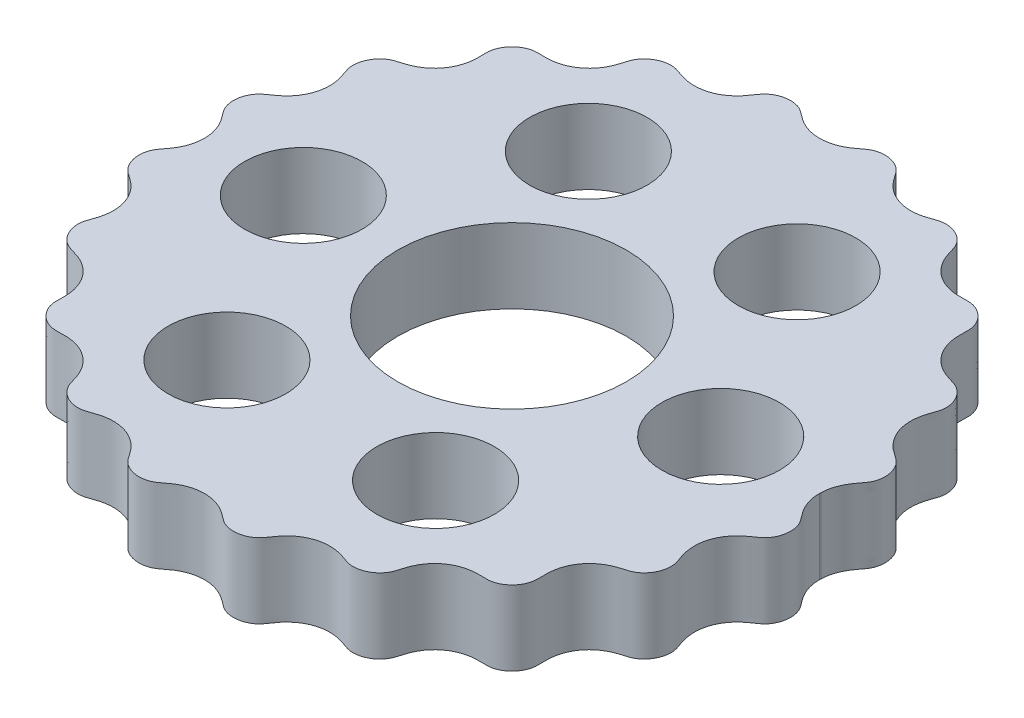
SolidWorks part; units mm, degrees
ref_plane "Front Plane" through (0, 0, 0) normal (0, 0, 1) x (1, 0, 0)
ref_plane "Top Plane" through (0, 0, 0) normal (0, 1, 0) x (1, 0, 0)
ref_plane "Right Plane" through (0, 0, 0) normal (1, 0, 0) x (0, 0, -1)
sketch "Cycloidal Base Sketch" plane through (0, 0, 0) normal (0, 1, 0) x (1, 0, 0)
  circle A0 centre (0, 0) radius 10.4
  spline S0 degree 4 poles (26.8059, 13.4572) (26.8639, 13.3205) (26.9582, 13.0381) (27.0247, 12.6393) (26.9913, 12.1833) (26.8931, 11.8403) (26.7874, 11.5481) (26.6811, 11.2558) (26.5654, 10.8802) (26.4695, 10.4144) (26.427, 9.9103) (26.4544, 9.3746) (26.5579, 8.8368) (26.741, 8.3075) (27.0736, 7.6723) (27.5036, 7.1396) (27.9833, 6.7262) (28.4638, 6.3979) (28.7892, 6.1843) (29.1138, 5.8878) (29.3918, 5.4852) (29.5767, 5.0325) (29.6654, 4.5525) (29.6681, 4.114) (29.6085, 3.728) (29.4888, 3.368) (29.3103, 3.046) (29.0925, 2.7659) (28.8808, 2.4963) (28.6821, 2.2162) (28.5035, 1.9231) (28.3483, 1.6165) (28.2193, 1.2987) (28.1286, 1.0033) (28.0684, 0.7391) (28.031, 0.4991) (28.0098, 0.3153) (27.9999, 0.0887) (27.9991, -0.0272) (28.0029, -0.1486) (28.0089, -0.265) (28.0175, -0.3782) (28.0354, -0.5324) (28.0698, -0.744) (28.1249, -0.9884) (28.2083, -1.2608) (28.3108, -1.5275) (28.4323, -1.7855) (28.5865, -2.0656) (28.7812, -2.3612) (29.0137, -2.6715) (29.2824, -2.9979) (29.5111, -3.3993) (29.6506, -3.8796) (29.6859, -4.4152) (29.5951, -4.9837) (29.3933, -5.4827) (29.1084, -5.8975) (28.762, -6.2072) (28.4035, -6.4354) (28.0263, -6.7018) (27.6432, -7.0237) (27.1801, -7.5243) (26.7185, -8.267) (26.4119, -9.2525) (26.4126, -10.2383) (26.5911, -11.0032) (26.7882, -11.5548) (26.927, -11.9205) (27.0435, -12.4984) (26.9493, -13.2923) (26.5792, -14.0112) (25.9799, -14.554) (25.4261, -14.7937) (25.0319, -14.8958) (24.5986, -15.0296) (24.1341, -15.2147) (23.6554, -15.4803) (23.1843, -15.841) (22.6738, -16.3739) (22.2038, -17.1251) (21.9508, -17.9268) (21.889, -18.705) (21.9078, -19.2869) (21.9249, -19.6752) (21.8711, -20.1112) (21.7056, -20.5711) (21.3378, -21.1537) (20.842, -21.5737) (20.3424, -21.8097) (19.8501, -21.9053) (19.5428, -21.9221) (19.1848, -21.902) (18.7291, -21.8953) (18.227, -21.9313) (17.5411, -22.0688) (16.7174, -22.4135) (15.8912, -23.0484) (15.3236, -23.8571) (15.0299, -24.5755) (14.8707, -25.1317) (14.766, -25.5035) (14.5781, -25.8973) (14.2781, -26.2796) (13.8632, -26.6219) (13.3335, -26.8852) (12.7989, -27.0092) (12.2906, -27.0113) (11.8436, -26.9022) (11.4606, -26.7512) (11.0257, -26.6054) (10.534, -26.4858) (9.8342, -26.4087) (8.9432, -26.4893) (8.1017, -26.7955) (7.3751, -27.2965) (6.9023, -27.7769) (6.6066, -28.1555) (6.3661, -28.5133) (6.1518, -28.8317) (5.8503, -29.1436) (5.4485, -29.4103) (4.9529, -29.6037) (4.3781, -29.688) (3.8872, -29.6483) (3.4999, -29.5378) (3.2176, -29.4051) (3.0274, -29.2892) (2.8036, -29.124) (2.5433, -28.9157) (2.201, -28.6662) (1.7577, -28.406) (1.2527, -28.191) (0.6884, -28.0437) (-0.0326, -27.9684) (-0.7557, -28.0384) (-1.4479, -28.2507) (-2.0404, -28.5633) (-2.4351, -28.8321) (-2.7715, -29.0973) (-3.073, -29.3309) (-3.4554, -29.5298) (-3.9177, -29.6561) (-4.4471, -29.6846) (-5.0196, -29.5854) (-5.5263, -29.3716) (-5.9011, -29.0996) (-6.1494, -28.8243) (-6.3429, -28.5502) (-6.5277, -28.2703) (-6.7787, -27.9261) (-7.1239, -27.5413) (-7.5425, -27.1814) (-8.039, -26.8689) (-8.7082, -26.5782) (-9.4242, -26.4275) (-10.1535, -26.4235) (-10.8129, -26.5457) (-11.2651, -26.6821) (-11.6572, -26.8284) (-12.0036, -26.9493) (-12.4193, -27.0163) (-12.8932, -26.9935) (-13.4055, -26.8567) (-13.9224, -26.5824) (-14.2973, -26.2558) (-14.5452, -25.9324) (-14.6935, -25.6538) (-14.7772, -25.4447) (-14.8598, -25.1759) (-14.9496, -24.8509) (-15.0843, -24.4441) (-15.2974, -23.9699) (-15.5891, -23.4974) (-15.9703, -23.0471) (-16.413, -22.6624) (-16.906, -22.3515) (-17.4366, -22.1197) (-17.9918, -21.9687) (-18.5102, -21.9036) (-18.9796, -21.8955) (-19.3952, -21.9141) (-19.7601, -21.9199) (-20.1734, -21.8522) (-20.6133, -21.6828) (-21.056, -21.3934) (-21.4613, -20.9716) (-21.716, -20.5431) (-21.8505, -20.1561) (-21.9036, -19.8431) (-21.9171, -19.6171) (-21.9114, -19.3343) (-21.8968, -18.9956) (-21.9008, -18.5646) (-21.96, -18.0451) (-22.0957, -17.5034) (-22.3246, -16.9559) (-22.6319, -16.4545) (-23.0085, -16.01) (-23.4431, -15.6306) (-23.9235, -15.3209) (-24.3946, -15.103) (-24.8364, -14.9529) (-25.2353, -14.8436) (-25.5816, -14.7347) (-25.9501, -14.5407) (-26.3123, -14.2435) (-26.6414, -13.8314) (-26.8948, -13.3044) (-27.0029, -12.8166) (-27.0091, -12.4045) (-26.9605, -12.0891) (-26.9016, -11.8691) (-26.8075, -11.6008) (-26.6887, -11.2811) (-26.5601, -10.8672) (-26.458, -10.3514) (-26.4232, -9.7908) (-26.4764, -9.1964) (-26.6191, -8.6243) (-26.8445, -8.0873) (-27.1437, -7.5965) (-27.5055, -7.1591) (-27.8858, -6.8108) (-28.2582, -6.5346) (-28.6022, -6.3092) (-28.8951, -6.0977) (-29.1816, -5.7989) (-29.4306, -5.4054) (-29.6132, -4.914) (-29.6894, -4.3381) (-29.6413, -3.8421) (-29.519, -3.4476) (-29.3472, -3.1076) (-29.1769, -2.8701) (-28.9943, -2.6435) (-28.7849, -2.3635) (-28.5715, -2.0475) (-28.3452, -1.633) (-28.1436, -1.1074) (-28.017, -0.526) (-27.9819, 0.0602) (-28.0354, 0.6372) (-28.1721, 1.192) (-28.3833, 1.7148) (-28.6382, 2.1591) (-28.9068, 2.5335) (-29.1632, 2.852) (-29.3734, 3.1437) (-29.5496, 3.5157) (-29.6618, 3.9648) (-29.6814, 4.4871) (-29.5742, 5.058) (-29.3729, 5.515) (-29.1317, 5.8532) (-28.9013, 6.0815) (-28.7173, 6.227) (-28.5238, 6.3592) (-28.3295, 6.4899) (-28.0903, 6.6589) (-27.7891, 6.8963) (-27.4455, 7.2241) (-27.0924, 7.6666) (-26.7946, 8.1855) (-26.5842, 8.7353) (-26.4618, 9.3014) (-26.4252, 9.8696) (-26.4682, 10.4278) (-26.5754, 10.9253) (-26.7159, 11.361) (-26.8609, 11.741) (-26.9676, 12.0823) (-27.0169, 12.4888) (-26.9825, 12.9476) (-26.8522, 13.4002) (-26.6322, 13.8255) (-26.3658, 14.1732) (-26.0763, 14.4443) (-25.7467, 14.6606) (-25.3843, 14.804) (-25.0132, 14.9019) (-24.6498, 15.0143) (-24.2055, 15.1839) (-23.698, 15.4481) (-23.1928, 15.8218) (-22.7276, 16.321) (-22.3767, 16.8567) (-22.1301, 17.403) (-21.9781, 17.9494) (-21.914, 18.4208) (-21.8983, 18.8047) (-21.9019, 19.0981) (-21.9104, 19.3326) (-21.9174, 19.5673) (-21.9082, 19.8021) (-21.8596, 20.1234) (-21.7283, 20.5183) (-21.4773, 20.9505) (-21.0789, 21.3732) (-20.6456, 21.6645) (-20.2176, 21.8382) (-19.814, 21.9152) (-19.4551, 21.9175) (-19.0475, 21.8972) (-18.5877, 21.8993) (-18.0794, 21.9532) (-17.5333, 22.0879) (-17.0042, 22.3017) (-16.5051, 22.596) (-16.0501, 22.968) (-15.6523, 23.412) (-15.3437, 23.8842) (-15.1405, 24.3114) (-15.0092, 24.6702) (-14.9231, 24.9491) (-14.8593, 25.1735) (-14.7931, 25.3975) (-14.7109, 25.6163) (-14.5642, 25.9042) (-14.3169, 26.2361) (-13.9442, 26.5673) (-13.4337, 26.8447) (-12.9296, 26.9863) (-12.4659, 27.0169) (-12.0563, 26.962) (-11.7134, 26.8503) (-11.3296, 26.7046) (-10.8884, 26.5654) (-10.3845, 26.4617) (-9.8193, 26.4248) (-9.2469, 26.4696) (-8.6797, 26.6011) (-8.1319, 26.8206) (-7.6179, 27.1262) (-7.1833, 27.4836) (-6.8246, 27.8695) (-6.5644, 28.2171) (-6.3751, 28.5015) (-6.2133, 28.736) (-6.0701, 28.9136) (-5.8435, 29.1393) (-5.5063, 29.3776) (-5.048, 29.5776) (-4.4728, 29.6829) (-3.9465, 29.6597) (-3.4939, 29.5424) (-3.1206, 29.3597) (-2.829, 29.1445) (-2.5068, 28.8863) (-2.1269, 28.6173) (-1.6752, 28.3639) (-1.144, 28.1564) (-0.5827, 28.0264) (-0.0019, 27.9813) (0.585, 28.0256) (1.164, 28.1611) (1.6834, 28.3689) (2.1399, 28.6261) (2.4919, 28.8762) (2.758, 29.0874) (2.9836, 29.2588) (3.1745, 29.3814) (3.4591, 29.5233) (3.8519, 29.643) (4.3485, 29.6895) (4.928, 29.6101) (5.4221, 29.4229) (5.8174, 29.1679) (6.1153, 28.8747) (6.3254, 28.5771) (6.5539, 28.2304) (6.8352, 27.8558) (7.1911, 27.4748) (7.6377, 27.1141) (8.1357, 26.8201) (8.6763, 26.6024) (9.2478, 26.4685) (9.8372, 26.4232) (10.3921, 26.4637) (10.9022, 26.5694) (11.3114, 26.6993) (11.6278, 26.8177) (11.8942, 26.9095) (12.1129, 26.9653) (12.4259, 27.0099) (12.834, 27.0001) (13.3192, 26.8894) (13.8452, 26.633) (14.257, 26.2998) (14.554, 25.9312) (14.7449, 25.5566) (14.8512, 25.2062) (14.9628, 24.8038) (15.1173, 24.3584) (15.4041, 23.754) (15.8339, 23.1659) (16.3749, 22.674) (17.0026, 22.3015) (17.5477, 22.0817) (18.0857, 21.9531) (18.6008, 21.899) (19.0277, 21.8976) (19.3633, 21.9128) (19.6435, 21.9166) (19.8673, 21.9006) (20.1767, 21.8445) (20.5589, 21.7078) (20.9822, 21.4527) (21.3992, 21.0485) (21.6877, 20.6041) (21.8577, 20.1572) (21.9226, 19.7321) (21.9116, 19.3517) (21.8945, 18.9246) (21.9082, 18.4482) (22.0019, 17.7864) (22.2349, 17.1018) (22.6013, 16.4748) (23.0847, 15.9341) (23.5355, 15.5623) (24.0065, 15.2784) (24.4781, 15.0715) (24.8818, 14.9405) (25.204, 14.8521) (25.4698, 14.7684) (25.6759, 14.683) (25.9502, 14.533) (26.2682, 14.2846) (26.5897, 13.9109) (26.8599, 13.3967) (26.9953, 12.8828) (27.0165, 12.402) (26.9428, 11.9755) (26.812, 11.6155) (26.6639, 11.2117) (26.531, 10.751) (26.419, 10.0878) (26.4384, 9.206) (26.6828, 8.3445) (27.1397, 7.5745) (27.6133, 7.0515) (27.9992, 6.7228) (28.3732, 6.4556) (28.7212, 6.2343) (29.0737, 5.9372) (29.3722, 5.5245) (29.587, 5.0189) (29.6859, 4.4357) (29.6537, 3.8993) (29.5217, 3.4328) (29.3154, 3.0494) (29.0766, 2.7466) (28.855, 2.4624) (28.6625, 2.1852) (28.5017, 1.9165) (28.3697, 1.659) (28.2562, 1.3927) (28.1621, 1.1193) (28.0976, 0.8742) (28.0555, 0.6601) (28.0321, 0.5046) (28.0196, 0.391) (28.0097, 0.2731) (28.0019, 0.1501) (27.999, 0.0339) (28.0017, -0.1944) (28.0172, -0.3789) (28.0404, -0.5678) (28.0694, -0.7323) (28.1083, -0.9116) (28.1593, -1.1041) (28.2315, -1.325) (28.3306, -1.5714) (28.4456, -1.8108) (28.6076, -2.1005) (28.7998, -2.3889) (29.0195, -2.6747) (29.2526, -2.9684) (29.4251, -3.2427) (29.5712, -3.5902) (29.6646, -4.0094) (29.6814, -4.6356) (29.5182, -5.2632) (29.2112, -5.7976) (28.789, -6.1854) (28.4595, -6.4) (28.104, -6.6445) (27.7365, -6.9392) (27.2807, -7.3993) (26.8581, -8.016) (26.5516, -8.7634) (26.4156, -9.6155) (26.4446, -10.2999) (26.5611, -10.8731) (26.6969, -11.301) (26.8049, -11.5957) (26.9184, -11.9123) (27.0024, -12.2627) (27.015, -12.6849) (26.9522, -13.0399) (26.88, -13.2686) (26.8371, -13.3802) knots 0 0 0 0 0 0.002533 0.005066 0.006835 0.00772 0.008605 0.010374 0.012143 0.014424 0.016705 0.018986 0.021267 0.023746 0.026226 0.031185 0.032844 0.034503 0.036162 0.037822 0.040301 0.04278 0.04444 0.046099 0.047759 0.049418 0.050882 0.052346 0.05381 0.055273 0.056737 0.058201 0.059665 0.061129 0.06199 0.062852 0.063714 0.064575 0.065184 0.065488 0.065792 0.0664 0.067009 0.068226 0.069443 0.07066 0.071876 0.073093 0.07431 0.076111 0.077913 0.079714 0.081515 0.083942 0.086368 0.088809 0.09125 0.093062 0.094873 0.096685 0.098497 0.100945 0.103394 0.108291 0.113293 0.118294 0.119961 0.121629 0.123296 0.124963 0.129954 0.134964 0.136702 0.138439 0.140177 0.141915 0.144438 0.146961 0.149485 0.152008 0.156981 0.161954 0.163611 0.165267 0.166924 0.16858 0.17106 0.17354 0.178581 0.179454 0.180328 0.182075 0.183822 0.18557 0.188108 0.190647 0.195724 0.200669 0.205614 0.20726 0.208906 0.210552 0.212197 0.214662 0.217127 0.219662 0.222197 0.223954 0.225711 0.227468 0.229224 0.231778 0.234332 0.23944 0.244357 0.246816 0.249274 0.250909 0.252544 0.254179 0.255814 0.258264 0.260713 0.263181 0.265648 0.266597 0.267546 0.268495 0.269443 0.271341 0.273239 0.275718 0.278197 0.280677 0.283156 0.288045 0.290489 0.292933 0.294557 0.296182 0.297806 0.299431 0.301865 0.304299 0.306781 0.309263 0.311171 0.312126 0.31308 0.314988 0.316897 0.319391 0.321884 0.324378 0.326872 0.331797 0.33426 0.336723 0.338285 0.339847 0.34141 0.342972 0.345429 0.347885 0.350381 0.352878 0.353837 0.354797 0.355756 0.356716 0.358635 0.360555 0.363063 0.365571 0.368079 0.370587 0.373034 0.37548 0.377927 0.380373 0.381927 0.383481 0.385035 0.386588 0.38903 0.391471 0.393982 0.396492 0.397457 0.398422 0.399387 0.400352 0.402282 0.404212 0.406735 0.409257 0.411779 0.414302 0.416732 0.419162 0.421593 0.424023 0.425568 0.427114 0.42866 0.430205 0.432631 0.435057 0.437582 0.440106 0.441077 0.442047 0.443017 0.443988 0.445929 0.44787 0.450406 0.452943 0.455479 0.458016 0.46043 0.462844 0.465258 0.467672 0.469209 0.470747 0.472284 0.473822 0.476232 0.478643 0.481152 0.483661 0.484655 0.485649 0.487638 0.488632 0.489626 0.491615 0.494144 0.496673 0.499201 0.50173 0.504128 0.506525 0.508923 0.51132 0.51285 0.514379 0.515909 0.517438 0.519834 0.522229 0.524752 0.527275 0.528275 0.529275 0.530274 0.531274 0.532274 0.533273 0.535273 0.537816 0.540358 0.542901 0.545444 0.547825 0.550206 0.552587 0.554968 0.556489 0.558011 0.559533 0.561055 0.563435 0.565816 0.567502 0.569188 0.570875 0.572561 0.574183 0.575806 0.577428 0.579051 0.582295 0.58554 0.588087 0.590635 0.593182 0.595729 0.597733 0.598734 0.599736 0.600737 0.601739 0.60274 0.603742 0.60627 0.608797 0.611188 0.613578 0.615105 0.616632 0.618159 0.619686 0.622078 0.624469 0.626861 0.629253 0.631787 0.63432 0.636854 0.639387 0.64138 0.642376 0.643372 0.644368 0.645364 0.64636 0.647356 0.64987 0.652383 0.654789 0.657195 0.658729 0.660264 0.661799 0.663334 0.665742 0.66815 0.670559 0.672967 0.675509 0.67805 0.680591 0.683133 0.685077 0.687022 0.687994 0.688966 0.689939 0.690911 0.69344 0.695969 0.69839 0.700811 0.702354 0.703897 0.70544 0.706982 0.709407 0.711832 0.714257 0.716681 0.719208 0.721736 0.724263 0.72679 0.728724 0.730658 0.731624 0.732591 0.733558 0.734525 0.73704 0.739555 0.741992 0.744428 0.745979 0.74753 0.749081 0.750632 0.753073 0.755514 0.757955 0.760396 0.762909 0.765422 0.767935 0.770448 0.772371 0.774294 0.775255 0.776216 0.777178 0.778139 0.78064 0.783141 0.785593 0.788044 0.789604 0.791163 0.792722 0.794282 0.796739 0.799196 0.804111 0.806609 0.809108 0.811607 0.814105 0.816018 0.81793 0.818886 0.819842 0.820798 0.821754 0.824241 0.826727 0.829157 0.831586 0.833207 0.834828 0.836448 0.838069 0.840509 0.842948 0.847826 0.850311 0.852795 0.855279 0.857763 0.859665 0.861566 0.862517 0.863468 0.864418 0.865369 0.867841 0.870314 0.872758 0.875202 0.876833 0.878465 0.880096 0.881728 0.884181 0.886635 0.891542 0.896661 0.89922 0.901779 0.903539 0.905299 0.907059 0.908819 0.91136 0.9139 0.91636 0.918819 0.920461 0.922103 0.923745 0.925387 0.926621 0.927855 0.929089 0.930323 0.931557 0.932791 0.933407 0.934024 0.934333 0.934641 0.935258 0.936122 0.936987 0.937851 0.938715 0.939281 0.939847 0.94098 0.942112 0.943245 0.944377 0.94551 0.947775 0.949153 0.950531 0.951909 0.953287 0.955556 0.957826 0.96251 0.964186 0.965863 0.96754 0.969216 0.971553 0.97389 0.978563 0.981882 0.9852 0.988519 0.990178 0.991837 0.992858 0.993878 0.995919 0.997959 1 1 1 1 1 construction
  spline S1 degree 4 poles (28, 0) (28, -0.031) (28.0007, -0.0776) (28.0029, -0.1486) (28.0089, -0.265) (28.0175, -0.3782) (28.0354, -0.5324) (28.0698, -0.744) (28.1249, -0.9884) (28.2083, -1.2608) (28.3108, -1.5275) (28.4323, -1.7855) (28.5865, -2.0656) (28.7812, -2.3612) (29.0137, -2.6715) (29.2824, -2.9979) (29.5111, -3.3993) (29.6506, -3.8796) (29.6859, -4.4152) (29.5951, -4.9837) (29.3933, -5.4827) (29.1084, -5.8975) (28.762, -6.2072) (28.4035, -6.4354) (28.0263, -6.7018) (27.6432, -7.0237) (27.1801, -7.5243) (26.7185, -8.267) (26.4119, -9.2525) (26.4126, -10.2383) (26.5911, -11.0032) (26.7882, -11.5548) (26.927, -11.9205) (27.0435, -12.4984) (26.9493, -13.2923) (26.5792, -14.0112) (25.9799, -14.554) (25.4261, -14.7937) (25.0319, -14.8958) (24.5986, -15.0296) (24.1341, -15.2147) (23.6554, -15.4803) (23.1843, -15.841) (22.6738, -16.3739) (22.2038, -17.1251) (21.9508, -17.9268) (21.889, -18.705) (21.9078, -19.2869) (21.9249, -19.6752) (21.8711, -20.1112) (21.7056, -20.5711) (21.3378, -21.1537) (20.842, -21.5737) (20.3424, -21.8097) (19.8501, -21.9053) (19.5428, -21.9221) (19.1848, -21.902) (18.7291, -21.8953) (18.227, -21.9313) (17.5411, -22.0688) (16.7174, -22.4135) (15.8912, -23.0484) (15.3236, -23.8571) (15.0299, -24.5755) (14.8707, -25.1317) (14.766, -25.5035) (14.5781, -25.8973) (14.2781, -26.2796) (13.8632, -26.6219) (13.3335, -26.8852) (12.7989, -27.0092) (12.2906, -27.0113) (11.8436, -26.9022) (11.4606, -26.7512) (11.0257, -26.6054) (10.534, -26.4858) (9.8342, -26.4087) (8.9432, -26.4893) (8.1017, -26.7955) (7.3751, -27.2965) (6.9023, -27.7769) (6.6066, -28.1555) (6.3661, -28.5133) (6.1518, -28.8317) (5.8503, -29.1436) (5.4485, -29.4103) (4.9529, -29.6037) (4.3781, -29.688) (3.8872, -29.6483) (3.4999, -29.5378) (3.2176, -29.4051) (3.0274, -29.2892) (2.8036, -29.124) (2.5433, -28.9157) (2.201, -28.6662) (1.7577, -28.406) (1.2527, -28.191) (0.6884, -28.0437) (-0.0326, -27.9684) (-0.7557, -28.0384) (-1.4479, -28.2507) (-2.0404, -28.5633) (-2.4351, -28.8321) (-2.7715, -29.0973) (-3.073, -29.3309) (-3.4554, -29.5298) (-3.9177, -29.6561) (-4.4471, -29.6846) (-5.0196, -29.5854) (-5.5263, -29.3716) (-5.9011, -29.0996) (-6.1494, -28.8243) (-6.3429, -28.5502) (-6.5277, -28.2703) (-6.7787, -27.9261) (-7.1239, -27.5413) (-7.5425, -27.1814) (-8.039, -26.8689) (-8.7082, -26.5782) (-9.4242, -26.4275) (-10.1535, -26.4235) (-10.8129, -26.5457) (-11.2651, -26.6821) (-11.6572, -26.8284) (-12.0036, -26.9493) (-12.4193, -27.0163) (-12.8932, -26.9935) (-13.4055, -26.8567) (-13.9224, -26.5824) (-14.2973, -26.2558) (-14.5452, -25.9324) (-14.6935, -25.6538) (-14.7772, -25.4447) (-14.8598, -25.1759) (-14.9496, -24.8509) (-15.0843, -24.4441) (-15.2974, -23.9699) (-15.5891, -23.4974) (-15.9703, -23.0471) (-16.413, -22.6624) (-16.906, -22.3515) (-17.4366, -22.1197) (-17.9918, -21.9687) (-18.5102, -21.9036) (-18.9796, -21.8955) (-19.3952, -21.9141) (-19.7601, -21.9199) (-20.1734, -21.8522) (-20.6133, -21.6828) (-21.056, -21.3934) (-21.4613, -20.9716) (-21.716, -20.5431) (-21.8505, -20.1561) (-21.9036, -19.8431) (-21.9171, -19.6171) (-21.9114, -19.3343) (-21.8968, -18.9956) (-21.9008, -18.5646) (-21.96, -18.0451) (-22.0957, -17.5034) (-22.3246, -16.9559) (-22.6319, -16.4545) (-23.0085, -16.01) (-23.4431, -15.6306) (-23.9235, -15.3209) (-24.3946, -15.103) (-24.8364, -14.9529) (-25.2353, -14.8436) (-25.5816, -14.7347) (-25.9501, -14.5407) (-26.3123, -14.2435) (-26.6414, -13.8314) (-26.8948, -13.3044) (-27.0029, -12.8166) (-27.0091, -12.4045) (-26.9605, -12.0891) (-26.9016, -11.8691) (-26.8075, -11.6008) (-26.6887, -11.2811) (-26.5601, -10.8672) (-26.458, -10.3514) (-26.4232, -9.7908) (-26.4764, -9.1964) (-26.6191, -8.6243) (-26.8445, -8.0873) (-27.1437, -7.5965) (-27.5055, -7.1591) (-27.8858, -6.8108) (-28.2582, -6.5346) (-28.6022, -6.3092) (-28.8951, -6.0977) (-29.1816, -5.7989) (-29.4306, -5.4054) (-29.6132, -4.914) (-29.6894, -4.3381) (-29.6413, -3.8421) (-29.519, -3.4476) (-29.3472, -3.1076) (-29.1769, -2.8701) (-28.9943, -2.6435) (-28.7849, -2.3635) (-28.5715, -2.0475) (-28.3452, -1.633) (-28.1436, -1.1074) (-28.017, -0.526) (-27.9819, 0.0602) (-28.0354, 0.6372) (-28.1721, 1.192) (-28.3833, 1.7148) (-28.6382, 2.1591) (-28.9068, 2.5335) (-29.1632, 2.852) (-29.3734, 3.1437) (-29.5496, 3.5157) (-29.6618, 3.9648) (-29.6814, 4.4871) (-29.5742, 5.058) (-29.3729, 5.515) (-29.1317, 5.8532) (-28.9013, 6.0815) (-28.7173, 6.227) (-28.5238, 6.3592) (-28.3295, 6.4899) (-28.0903, 6.6589) (-27.7891, 6.8963) (-27.4455, 7.2241) (-27.0924, 7.6666) (-26.7946, 8.1855) (-26.5842, 8.7353) (-26.4618, 9.3014) (-26.4252, 9.8696) (-26.4682, 10.4278) (-26.5754, 10.9253) (-26.7159, 11.361) (-26.8609, 11.741) (-26.9676, 12.0823) (-27.0169, 12.4888) (-26.9825, 12.9476) (-26.8522, 13.4002) (-26.6322, 13.8255) (-26.3658, 14.1732) (-26.0763, 14.4443) (-25.7467, 14.6606) (-25.3843, 14.804) (-25.0132, 14.9019) (-24.6498, 15.0143) (-24.2055, 15.1839) (-23.698, 15.4481) (-23.1928, 15.8218) (-22.7276, 16.321) (-22.3767, 16.8567) (-22.1301, 17.403) (-21.9781, 17.9494) (-21.914, 18.4208) (-21.8983, 18.8047) (-21.9019, 19.0981) (-21.9104, 19.3326) (-21.9174, 19.5673) (-21.9082, 19.8021) (-21.8596, 20.1234) (-21.7283, 20.5183) (-21.4773, 20.9505) (-21.0789, 21.3732) (-20.6456, 21.6645) (-20.2176, 21.8382) (-19.814, 21.9152) (-19.4551, 21.9175) (-19.0475, 21.8972) (-18.5877, 21.8993) (-18.0794, 21.9532) (-17.5333, 22.0879) (-17.0042, 22.3017) (-16.5051, 22.596) (-16.0501, 22.968) (-15.6523, 23.412) (-15.3437, 23.8842) (-15.1405, 24.3114) (-15.0092, 24.6702) (-14.9231, 24.9491) (-14.8593, 25.1735) (-14.7931, 25.3975) (-14.7109, 25.6163) (-14.5642, 25.9042) (-14.3169, 26.2361) (-13.9442, 26.5673) (-13.4337, 26.8447) (-12.9296, 26.9863) (-12.4659, 27.0169) (-12.0563, 26.962) (-11.7134, 26.8503) (-11.3296, 26.7046) (-10.8884, 26.5654) (-10.3845, 26.4617) (-9.8193, 26.4248) (-9.2469, 26.4696) (-8.6797, 26.6011) (-8.1319, 26.8206) (-7.6179, 27.1262) (-7.1833, 27.4836) (-6.8246, 27.8695) (-6.5644, 28.2171) (-6.3751, 28.5015) (-6.2133, 28.736) (-6.0701, 28.9136) (-5.8435, 29.1393) (-5.5063, 29.3776) (-5.048, 29.5776) (-4.4728, 29.6829) (-3.9465, 29.6597) (-3.4939, 29.5424) (-3.1206, 29.3597) (-2.829, 29.1445) (-2.5068, 28.8863) (-2.1269, 28.6173) (-1.6752, 28.3639) (-1.144, 28.1564) (-0.5827, 28.0264) (-0.0019, 27.9813) (0.585, 28.0256) (1.164, 28.1611) (1.6834, 28.3689) (2.1399, 28.6261) (2.4919, 28.8762) (2.758, 29.0874) (2.9836, 29.2588) (3.1745, 29.3814) (3.4591, 29.5233) (3.8519, 29.643) (4.3485, 29.6895) (4.928, 29.6101) (5.4221, 29.4229) (5.8174, 29.1679) (6.1153, 28.8747) (6.3254, 28.5771) (6.5539, 28.2304) (6.8352, 27.8558) (7.1911, 27.4748) (7.6377, 27.1141) (8.1357, 26.8201) (8.6763, 26.6024) (9.2478, 26.4685) (9.8372, 26.4232) (10.3921, 26.4637) (10.9022, 26.5694) (11.3114, 26.6993) (11.6278, 26.8177) (11.8942, 26.9095) (12.1129, 26.9653) (12.4259, 27.0099) (12.834, 27.0001) (13.3192, 26.8894) (13.8452, 26.633) (14.257, 26.2998) (14.554, 25.9312) (14.7449, 25.5566) (14.8512, 25.2062) (14.9628, 24.8038) (15.1173, 24.3584) (15.4041, 23.754) (15.8339, 23.1659) (16.3749, 22.674) (17.0026, 22.3015) (17.5477, 22.0817) (18.0857, 21.9531) (18.6008, 21.899) (19.0277, 21.8976) (19.3633, 21.9128) (19.6435, 21.9166) (19.8673, 21.9006) (20.1767, 21.8445) (20.5589, 21.7078) (20.9822, 21.4527) (21.3992, 21.0485) (21.6877, 20.6041) (21.8577, 20.1572) (21.9226, 19.7321) (21.9116, 19.3517) (21.8945, 18.9246) (21.9082, 18.4482) (22.0019, 17.7864) (22.2349, 17.1018) (22.6013, 16.4748) (23.0847, 15.9341) (23.5355, 15.5623) (24.0065, 15.2784) (24.4781, 15.0715) (24.8818, 14.9405) (25.204, 14.8521) (25.4698, 14.7684) (25.6759, 14.683) (25.9502, 14.533) (26.2682, 14.2846) (26.5897, 13.9109) (26.8599, 13.3967) (26.9953, 12.8828) (27.0165, 12.402) (26.9428, 11.9755) (26.812, 11.6155) (26.6639, 11.2117) (26.531, 10.751) (26.419, 10.0878) (26.4384, 9.206) (26.6828, 8.3445) (27.1397, 7.5745) (27.6133, 7.0515) (27.9992, 6.7228) (28.3732, 6.4556) (28.7212, 6.2343) (29.0737, 5.9372) (29.3722, 5.5245) (29.587, 5.0189) (29.6859, 4.4357) (29.6537, 3.8993) (29.5217, 3.4328) (29.3154, 3.0494) (29.0766, 2.7466) (28.855, 2.4624) (28.6625, 2.1852) (28.5017, 1.9165) (28.3697, 1.659) (28.2562, 1.3927) (28.1621, 1.1193) (28.0976, 0.8742) (28.0555, 0.6601) (28.0321, 0.5046) (28.0196, 0.391) (28.0097, 0.2731) (28.0051, 0.2008) (28.003, 0.1536) (28.002, 0.1221) knots 0.064575 0.064575 0.064575 0.064575 0.064575 0.065184 0.065488 0.065792 0.0664 0.067009 0.068226 0.069443 0.07066 0.071876 0.073093 0.07431 0.076111 0.077913 0.079714 0.081515 0.083942 0.086368 0.088809 0.09125 0.093062 0.094873 0.096685 0.098497 0.100945 0.103394 0.108291 0.113293 0.118294 0.119961 0.121629 0.123296 0.124963 0.129954 0.134964 0.136702 0.138439 0.140177 0.141915 0.144438 0.146961 0.149485 0.152008 0.156981 0.161954 0.163611 0.165267 0.166924 0.16858 0.17106 0.17354 0.178581 0.179454 0.180328 0.182075 0.183822 0.18557 0.188108 0.190647 0.195724 0.200669 0.205614 0.20726 0.208906 0.210552 0.212197 0.214662 0.217127 0.219662 0.222197 0.223954 0.225711 0.227468 0.229224 0.231778 0.234332 0.23944 0.244357 0.246816 0.249274 0.250909 0.252544 0.254179 0.255814 0.258264 0.260713 0.263181 0.265648 0.266597 0.267546 0.268495 0.269443 0.271341 0.273239 0.275718 0.278197 0.280677 0.283156 0.288045 0.290489 0.292933 0.294557 0.296182 0.297806 0.299431 0.301865 0.304299 0.306781 0.309263 0.311171 0.312126 0.31308 0.314988 0.316897 0.319391 0.321884 0.324378 0.326872 0.331797 0.33426 0.336723 0.338285 0.339847 0.34141 0.342972 0.345429 0.347885 0.350381 0.352878 0.353837 0.354797 0.355756 0.356716 0.358635 0.360555 0.363063 0.365571 0.368079 0.370587 0.373034 0.37548 0.377927 0.380373 0.381927 0.383481 0.385035 0.386588 0.38903 0.391471 0.393982 0.396492 0.397457 0.398422 0.399387 0.400352 0.402282 0.404212 0.406735 0.409257 0.411779 0.414302 0.416732 0.419162 0.421593 0.424023 0.425568 0.427114 0.42866 0.430205 0.432631 0.435057 0.437582 0.440106 0.441077 0.442047 0.443017 0.443988 0.445929 0.44787 0.450406 0.452943 0.455479 0.458016 0.46043 0.462844 0.465258 0.467672 0.469209 0.470747 0.472284 0.473822 0.476232 0.478643 0.481152 0.483661 0.484655 0.485649 0.487638 0.488632 0.489626 0.491615 0.494144 0.496673 0.499201 0.50173 0.504128 0.506525 0.508923 0.51132 0.51285 0.514379 0.515909 0.517438 0.519834 0.522229 0.524752 0.527275 0.528275 0.529275 0.530274 0.531274 0.532274 0.533273 0.535273 0.537816 0.540358 0.542901 0.545444 0.547825 0.550206 0.552587 0.554968 0.556489 0.558011 0.559533 0.561055 0.563435 0.565816 0.567502 0.569188 0.570875 0.572561 0.574183 0.575806 0.577428 0.579051 0.582295 0.58554 0.588087 0.590635 0.593182 0.595729 0.597733 0.598734 0.599736 0.600737 0.601739 0.60274 0.603742 0.60627 0.608797 0.611188 0.613578 0.615105 0.616632 0.618159 0.619686 0.622078 0.624469 0.626861 0.629253 0.631787 0.63432 0.636854 0.639387 0.64138 0.642376 0.643372 0.644368 0.645364 0.64636 0.647356 0.64987 0.652383 0.654789 0.657195 0.658729 0.660264 0.661799 0.663334 0.665742 0.66815 0.670559 0.672967 0.675509 0.67805 0.680591 0.683133 0.685077 0.687022 0.687994 0.688966 0.689939 0.690911 0.69344 0.695969 0.69839 0.700811 0.702354 0.703897 0.70544 0.706982 0.709407 0.711832 0.714257 0.716681 0.719208 0.721736 0.724263 0.72679 0.728724 0.730658 0.731624 0.732591 0.733558 0.734525 0.73704 0.739555 0.741992 0.744428 0.745979 0.74753 0.749081 0.750632 0.753073 0.755514 0.757955 0.760396 0.762909 0.765422 0.767935 0.770448 0.772371 0.774294 0.775255 0.776216 0.777178 0.778139 0.78064 0.783141 0.785593 0.788044 0.789604 0.791163 0.792722 0.794282 0.796739 0.799196 0.804111 0.806609 0.809108 0.811607 0.814105 0.816018 0.81793 0.818886 0.819842 0.820798 0.821754 0.824241 0.826727 0.829157 0.831586 0.833207 0.834828 0.836448 0.838069 0.840509 0.842948 0.847826 0.850311 0.852795 0.855279 0.857763 0.859665 0.861566 0.862517 0.863468 0.864418 0.865369 0.867841 0.870314 0.872758 0.875202 0.876833 0.878465 0.880096 0.881728 0.884181 0.886635 0.891542 0.896661 0.89922 0.901779 0.903539 0.905299 0.907059 0.908819 0.91136 0.9139 0.91636 0.918819 0.920461 0.922103 0.923745 0.925387 0.926621 0.927855 0.929089 0.930323 0.931557 0.932791 0.933407 0.934024 0.934333 0.934641 0.935258 0.935258 0.935258 0.935258 0.935258
  spline S2 degree 1 poles (28, 0) (28.002, 0.1221) knots 0 0 1 1
  dimension "D1" = 20.8
extrude "Cycloidal Base Extrusion" add sketch "Cycloidal Base Sketch" along normal blind 6.8
ref_axis "Center Axis" through (0, 6.8, 0) along (0, -1, 0)
sketch "Output Holes Sketch" plane through (0, 6.8, 0) normal (0, 1, 0) x (1, 0, 0)
  circle A0 centre (0, 0) radius 19 construction
  circle A1 centre (-19, 0) radius 5.35
  circle A2 centre (-9.5, 16.4545) radius 5.35
  circle A3 centre (9.5, 16.4545) radius 5.35
  circle A4 centre (19, 0) radius 5.35
  circle A5 centre (9.5, -16.4545) radius 5.35
  circle A6 centre (-9.5, -16.4545) radius 5.35
  point P15 (0, 0)
  dimension "D1" = 38
  dimension "D2" = 10.7
  dimension "D3" = 6
extrude "Output Holes Cutout" cut sketch "Output Holes Sketch" against normal through all
fillet "Top and Bottom Edge Fillet" [suppressed] radius 0.5
equation "\"Inner Hole\"= 20.80"
equation "\"D1@Cycloidal Base Sketch\" = \"Inner Hole\""
equation "\"Output Diameter\"= 9 + ( 1 * 2 ) - 0.3"
equation "\"D2@Output Holes Sketch\" = \"Output Diameter\""
equation "\"Hole Pattern Diameter\"= 38"
equation "\"D1@Output Holes Sketch\" = \"Hole Pattern Diameter\""
equation "\"Margin\"=0.5"
